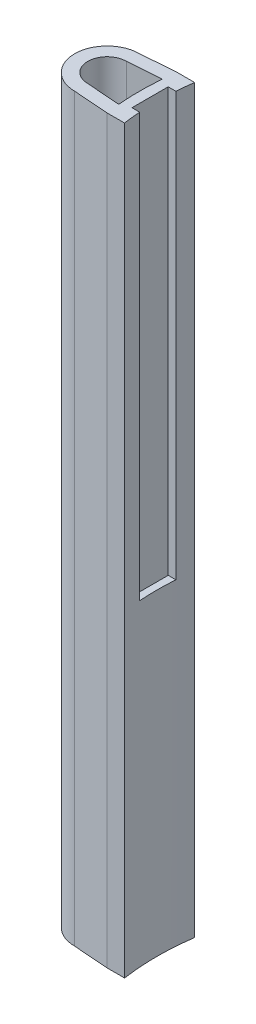
SolidWorks part; units mm, degrees
ref_plane "Front Plane" through (0, 0, 0) normal (0, 0, 1) x (1, 0, 0)
ref_plane "Top Plane" through (0, 0, 0) normal (0, 1, 0) x (1, 0, 0)
ref_plane "Right Plane" through (0, 0, 0) normal (1, 0, 0) x (0, 0, -1)
sketch "Sketch2" plane through (0, 0, 0) normal (0, 1, 0) x (1, 0, 0)
  line L0 (0, 2.775) -> (2.9759, 3)
  line L1 (0, -2.775) -> (2.9759, -3)
  line L2 (2.9759, -3) -> (4.4904, -3)
  line L3 (2.9759, 3) -> (4.4904, 3)
  line L4 (0, 1.65) -> (2.8525, 1.8657)
  line L5 (0, -1.65) -> (2.8525, -1.8657)
  arc A0 (0, 1.65) -> (0, -1.65) centre (0, 0) ccw
  arc A1 (0, 2.775) -> (0, -2.775) centre (0, 0) ccw
  arc A2 (2.8525, 1.8657) -> (2.8525, -1.8657) centre (25.275, 0) ccw
  arc A3 (4.4904, 3) -> (4.4904, -3) centre (25.275, 0) ccw
  arc A4 (4.4904, -3) -> (4.4904, 3) centre (25.275, 0) ccw construction
  arc A5 (2.9759, -3) -> (2.9759, 3) centre (25.275, 0) ccw construction
  arc A6 (2.8525, -1.8657) -> (2.9759, -3) centre (25.275, 0) ccw construction
  arc A7 (2.9759, 3) -> (2.8525, 1.8657) centre (25.275, 0) ccw construction
  arc A8 (0, -1.65) -> (0, 1.65) centre (0, 0) ccw construction
  arc A9 (2.775, 0) -> (2.1042, 1.8091) centre (0, 0) ccw construction
  arc A10 (2.1042, -1.8091) -> (2.775, 0) centre (0, 0) ccw construction
  arc A11 (0, -2.775) -> (2.1042, -1.8091) centre (0, 0) ccw construction
  arc A12 (2.1042, 1.8091) -> (0, 2.775) centre (0, 0) ccw construction
  point P9 (2.775, 0)
  dimension "D1" = 3.3
  dimension "D2" = 5.55
  dimension "D3" = 45
  dimension "D4" = 42
  dimension "D5" = 3
  dimension "D6" = 3
extrude "Boss-Extrude1" add sketch "Sketch2" along normal blind 63.33
sketch "Sketch3" plane through (0, 63.33, 0) normal (0, 1, 0) x (1, 0, 0)
  line L0 (4.3323, 1.55) -> (4.875, 1.55) construction
  line L1 (3.675, 1.55) -> (4.3323, 1.55)
  line L2 (3.675, 1.55) -> (3.675, -1.55)
  line L3 (3.675, -1.55) -> (4.3323, -1.55)
  line L4 (4.875, 1.55) -> (4.875, -1.55) construction
  line L5 (3.675, 1.55) -> (4.875, -1.55) construction
  line L6 (3.675, -1.55) -> (4.875, 1.55) construction
  line L7 (4.3323, -1.55) -> (4.875, -1.55) construction
  arc A0 (4.4904, 3) -> (4.4904, -3) centre (25.275, 0) ccw construction
  arc A1 (4.3323, 1.55) -> (4.3323, -1.55) centre (25.275, 0) ccw
  arc A2 (4.4904, 3) -> (4.3323, 1.55) centre (25.275, 0) ccw construction
  arc A3 (4.3323, -1.55) -> (4.4904, -3) centre (25.275, 0) ccw construction
  point P3 (4.275, 0)
  point P8 (0, 0)
  dimension "D1" = 3.1
  dimension "D2" = 0.6
extrude "Cut-Extrude1" cut sketch "Sketch3" against normal blind 36.1886
equation "\"ROD_OD\"= 3.25mm"
equation "\"ID\"= \"ROD_OD\" + 0.05mm'OF LUG"
equation "\"OD\"= \"ID\" + 2.25mm"
equation "\"BW\"= 6mm'LUG BASE WIDTH"
equation "\"BL\"= 63.33mm'LUG BASE LENGTH"
equation "\"ROCKET_OD\"= 42mm"
equation "\"D1@Sketch2\"=\"ID\""
equation "\"D2@Sketch2\"=\"OD\""
equation "\"D3@Sketch2\"=\"ROCKET_OD\"+3MM"
equation "\"D4@Sketch2\"=\"ROCKET_OD\""
equation "\"D5@Sketch2\"=\"BW\"/2"
equation "\"D6@Sketch2\"=\"BW\"/2"
equation "\"D1@Boss-Extrude1\"=\"BL\""
equation "\"D1@Cut-Extrude1\"=\"BL\"*4/7"
